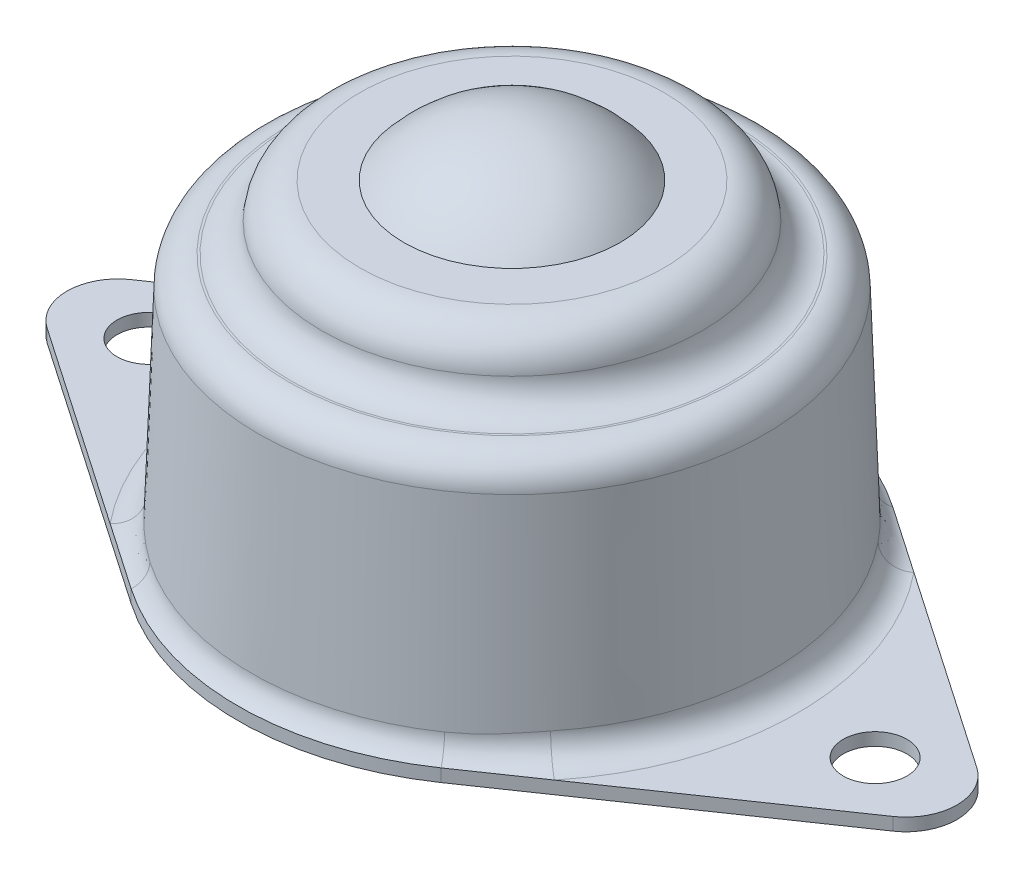
SolidWorks part; units mm, degrees
ref_plane "Front Plane" through (0, 0, 0) normal (0, 0, 1) x (1, 0, 0)
ref_plane "Top Plane" through (0, 0, 0) normal (0, 1, 0) x (1, 0, 0)
ref_plane "Right Plane" through (0, 0, 0) normal (1, 0, 0) x (0, 0, -1)
sketch "Sketch1" plane through (0, 0, 0) normal (0, 1, 0) x (1, 0, 0)
  line L0 (-81.7884, 0) -> (81.7884, 0) construction
  line L4 (0, 40.9345) -> (0, -40.9345) construction
  line L5 (-38, 12.0684) -> (-38, -12.0684) construction
  line L6 (-38, 0) -> (-12.1645, 17.7278)
  line L7 (38, 0) -> (12.1645, 17.7278)
  line L8 (38, 0) -> (12.1645, -17.7278)
  line L9 (-38, 0) -> (-12.1645, -17.7278)
  arc A0 (-12.1645, -17.7278) -> (12.1645, -17.7278) centre (0, 0) ccw
  arc A1 (12.1645, 17.7278) -> (-12.1645, 17.7278) centre (0, 0) ccw
  point P1 (0, 0)
  point P6 (0, 0)
  point P9 (0, 0)
  point P12 (38, 0)
  point P17 (-38, 0)
  dimension "D1" = 43
  dimension "D2" = 38
extrude "Boss-Extrude1" add sketch "Sketch1" along normal blind 1
sketch "Sketch2" plane through (0, 1, 0) normal (0, 1, 0) x (1, 0, 0)
  circle A0 centre (0, 0) radius 20.5
  dimension "D1" = 41
extrude "Boss-Extrude2" add sketch "Sketch2" along normal blind 20 draft 2
sketch "Sketch4" plane through (0, 21, 0) normal (0, 1, 0) x (1, 0, 0)
  circle A0 centre (0, 0) radius 15
  dimension "D1" = 30
extrude "Boss-Extrude3" add sketch "Sketch4" along normal blind 5 draft 2
sketch "Sketch5" plane through (0, 0, 0) normal (1, 0, 0) x (0, 0, -1)
  line L5 (0, 26) -> (8.4853, 26)
  line L8 (0, 26) -> (0, 30)
  arc A2 (8.4853, 26) -> (0, 30) centre (0, 19) ccw
ref_axis "Axis1" through (0, -10.4918, 0) along (0, 1, 0)
revolve "Revolve3" add sketch "Sketch5" angle 360 about axis through (0, -10.4918, 0) along (0, 1, 0)
fillet "Fillet2" radius 2.4 2 edges at (0, 21, 19.8016) (0, 21, 15)
fillet "Fillet3" radius 2 1 edges at (0, 1, 20.5)
fillet "Fillet4" radius 3 1 edges at (0, 26, 14.8254)
ref_axis "Axis2" through (0, 0, -28.4017) along (0, 0, 1)
hole_wizard "Ø5.0mm Dowel Hole1" positions "Sketch10" profile "Sketch11" hole size "Ø5.0" standard "ANSI Metric"
sketch "Sketch10" plane through (0, 1, 0) normal (0, 1, 0) x (1, 0, 0)
  line L0 (0, 28.4017) -> (0, -31.5959) construction
  point P0 (-28.5, 0)
  point P2 (28.5, 0)
  dimension "D1" = 57
  dimension "D2" = 28.5
sketch "Sketch11" plane through (-28.5, 1, 0) normal (1, 0, 0) x (0, 0, 1)
  line L0 (0, 0) -> (0, 8.0022)
  line L1 (0, 8.0022) -> (2.5, 6.5)
  line L2 (2.5, 6.5) -> (2.5, 0)
  line L5 (2.5, 0) -> (0, 0)
  line L10 (0, 8.0022) -> (-2.5, 6.5) construction
  line L11 (0, -6.35) -> (0, 107.95) construction
  dimension "Hole Dia." = 5
  dimension "Hole Depth" = 6.5
  dimension "Drill Angle" = 118
fillet "Fillet5" radius 4 2 edges at (38, 0.5, 0) (-38, 0.5, 0)
